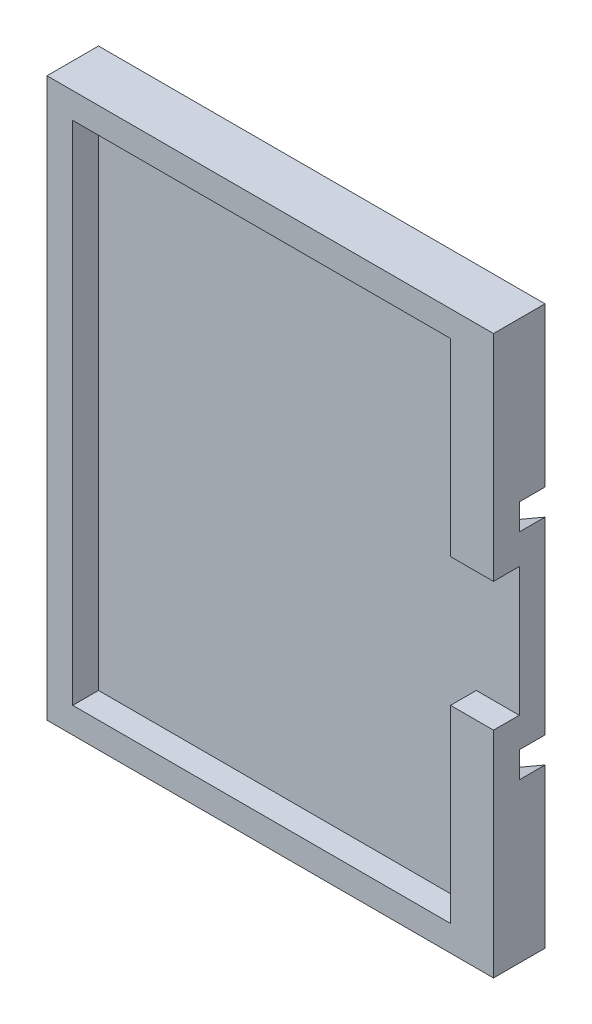
SolidWorks part; units mm, degrees
ref_plane "Front Plane" through (0, 0, 0) normal (0, 0, 1) x (1, 0, 0)
ref_plane "Top Plane" through (0, 0, 0) normal (0, 1, 0) x (1, 0, 0)
ref_plane "Right Plane" through (0, 0, 0) normal (1, 0, 0) x (0, 0, -1)
sketch "Sketch1" plane through (0, 0, 0) normal (0, 0, 1) x (1, 0, 0)
  line L0 (0, 0) -> (-40751.263, 0) construction
  line L1 (-40, -65) -> (64, -65)
  line L3 (-40, 65) -> (64, 65)
  line L4 (64, -65) -> (64, -28.0278)
  line L7 (15, 17) -> (49, 17)
  line L8 (15, 17) -> (15, -17)
  line L9 (15, -17) -> (49, -17)
  line L10 (49, 17) -> (49, -17)
  line L11 (0, 0) -> (0, 40751.263) construction
  line L20 (15, -23) -> (15, -57)
  line L21 (15, -23) -> (49, -23)
  line L22 (49, -23) -> (49, -57)
  line L23 (15, -57) -> (49, -57)
  line L24 (15, -118.7352) -> (15, -152.7352) [skipped]
  line L25 (15, -118.7352) -> (49, -118.7352) [skipped]
  line L26 (49, -118.7352) -> (49, -152.7352) [skipped]
  line L27 (15, -152.7352) -> (49, -152.7352) [skipped]
  line L28 (15, -158.7352) -> (15, -192.7352) [skipped]
  line L29 (15, -158.7352) -> (49, -158.7352) [skipped]
  line L30 (49, -158.7352) -> (49, -192.7352) [skipped]
  line L31 (15, -192.7352) -> (49, -192.7352) [skipped]
  line L32 (15, 57) -> (15, 23)
  line L33 (15, 57) -> (49, 57)
  line L34 (49, 57) -> (49, 23)
  line L35 (15, 23) -> (49, 23)
  line L52 (64, 21.9722) -> (64, -21.9722)
  line L53 (64, -22.1188) -> (56, -17.5) construction
  line L54 (56, -17.5) -> (56, -32.5) construction
  line L55 (56, -32.5) -> (64, -27.8812) construction
  line L60 (64, -21.9722) -> (64, 21.9722)
  line L61 (64, 28.0278) -> (64, 65)
  line L62 (64.0635, -22.0088) -> (55.873, -17.28) construction
  line L63 (55.873, -32.72) -> (64.0635, -27.9912) construction
  line L64 (55.873, 32.72) -> (64, 28.0278)
  line L65 (64, -21.9722) -> (55.873, -17.28)
  line L66 (55.873, -17.28) -> (55.873, -32.72)
  line L67 (55.873, -32.72) -> (64, -28.0278)
  line L68 (64, 21.9722) -> (55.873, 17.28)
  line L69 (55.873, 17.28) -> (55.873, 32.72)
  line L70 (64, -22.1188) -> (64, -27.8812) construction
  line L71 (-40, 65) -> (-40, -65)
  point P0 (0, 0)
  point P14 (15, 0)
  point P62 (55.873, -25)
  dimension "D1" = 34
  dimension "D2" = 34
  dimension "D3" = 15
  dimension "D6" = 8
  dimension "D7" = 15
  dimension "D8" = 6
  dimension "D10" = 6
  dimension "D11" = 8
  dimension "D12" = 60
  dimension "D13" = 60
  dimension "D14" = 8.127
  dimension "D15" = 15.4399
  dimension "D16" = 8
  dimension "D17" = 104
  dimension "D19" = 25
  dimension "D4" = 2
  dimension "D5" = 2
  dimension "D9" = 2
extrude "Boss-Extrude1" add sketch "Sketch1" along normal blind 6 contours L68 L69 L64 L61 L3 L1 L4 L67 L66 L65 L52 L7 L10 L9 L8 L23 L20 L21 L22 L35 L32 L33 L34 | L10 L7 L8 L9 | L32 L35 L34 L33 | L20 L23 L22 L21 region at (4.1405, 0, 0) region at (32, 0, 0) region at (32, -40, 0) region at (32, 40, 0)
sketch "Sketch2" plane through (0, 0, 6) normal (0, 0, 1) x (1, 0, 0)
  line L1 (-40, 65) -> (64, 65)
  line L3 (-40, -65) -> (64, -65)
  line L4 (64, 65) -> (64, 15)
  line L8 (0, 0) -> (115.6244, 0) construction
  line L9 (54, 15) -> (64, 15)
  line L10 (54, -15) -> (64, -15)
  line L12 (54, 59) -> (54, 15)
  line L13 (64, -15) -> (64, -65)
  line L17 (54, -15) -> (54, -59)
  line L18 (-54, -55) -> (54, -55) construction
  line L19 (-54, 55) -> (54, 55) construction
  line L20 (-54, 55) -> (-54, -55) construction
  line L21 (-34, -59) -> (54, -59)
  line L23 (-34, 59) -> (54, 59)
  line L24 (54, 55) -> (54, 15) construction
  line L25 (54, -15) -> (54, -55) construction
  line L26 (-58, -59) -> (64, -59) construction
  line L27 (-58, 59) -> (64, 59) construction
  line L28 (-40, 65) -> (-40, -65)
  line L29 (-34, 59) -> (-34, -59)
  line L30 (-64, 65) -> (64, 65) construction
  line L31 (-58, 59) -> (-58, -59) construction
  line L32 (-64, 65) -> (-64, -65) construction
  line L33 (-64, -65) -> (64, -65) construction
  line L34 (-34, 65) -> (-34, -65) construction
  dimension "D2" = 15
  dimension "D1" = 10
  dimension "D3" = 6
  dimension "D4" = 6
extrude "Boss-Extrude2" add sketch "Sketch2" along normal blind 6
